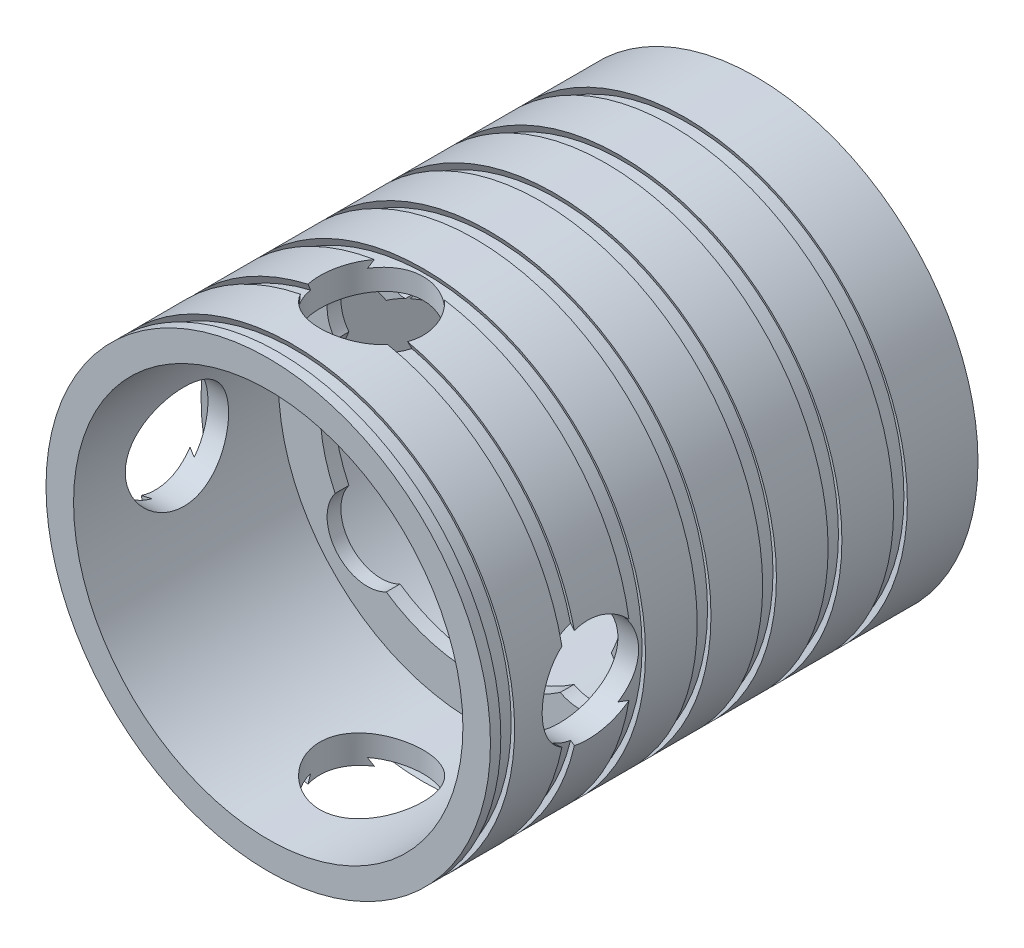
SolidWorks part; units mm, degrees
material "PA Type 6"
ref_plane "Front Plane" through (0, 0, 0) normal (0, 0, 1) x (1, 0, 0)
ref_plane "Top Plane" through (0, 0, 0) normal (0, 1, 0) x (1, 0, 0)
ref_plane "Right Plane" through (0, 0, 0) normal (1, 0, 0) x (0, 0, -1)
sketch "main_features" plane through (0, 0, 0) normal (0, 0, 1) x (1, 0, 0)
  line L0 (0, -22.25) -> (0, 22.25) construction
  line L1 (-22.25, 0) -> (22.25, 0) construction
  line L2 (10.9973, -19.3422) -> (-10.9973, -19.3422)
  line L3 (10.9973, 19.3422) -> (-10.9973, 19.3422)
  line L4 (-27.25, -7.4498) -> (-27.25, 7.4498)
  line L5 (27.25, -7.4498) -> (27.25, 7.4498)
  line L7 (-27, -7.2801) -> (-27, 7.2801) construction
  circle A0 centre (0, 0) radius 28.25
  circle A1 centre (0, 0) radius 32.25
  circle A2 centre (0, 0) radius 22.25
  circle A3 centre (-10.1595, 21.5294) radius 1.6
  arc A4 (26.963, 7.5497) -> (-26.963, 7.5497) centre (0, 0) ccw construction
  circle A11 centre (-10.1595, 21.5294) radius 1.6 construction
  circle A12 centre (-15.3592, 13.1518) radius 5.8499
  circle A13 centre (-15.3592, 13.1518) radius 5.8499 construction
  circle A14 centre (15.3592, 13.1518) radius 5.6
  circle A15 centre (15.3592, 13.1518) radius 5.6 construction
  circle A16 centre (-15.3592, -13.1518) radius 5.8499
  circle A17 centre (15.3592, -13.1518) radius 5.8499
  circle A18 centre (15.3592, 13.1518) radius 5.8499
  dimension "D1" = 6
  dimension "D2" = 4
  dimension "D3" = 0.25
  dimension "D4" = 0.25
extrude "front_sleeve" add sketch "main_features" against normal up to surface (39 mm away) contours A1 A0 | L5 A0 | L4 A0 region at (-27.6506, 0, 0) region at (27.6506, 0, 0) region at (-31.3378, 0, 0)
extrude "middle_flange" add sketch "Sketch1<3>" along normal blind 2 contours A1 A0 | L4 A0 | L5 A0 L4 A2 A18 A17 A16 A12 A3 | L5 A0 region at (-27.6506, 0, 0) region at (-26.465, 0, 0) region at (27.6506, 0, 0) region at (-31.3378, 0, 0)
sketch "Sketch1<3>" plane through (0, 0, 0) normal (0, 0, 1) x (1, 0, 0) same geometry as "main_features"
extrude "back_sleeve" add sketch "Sketch1<4>" along normal blind 31.75 contours A1 A0 region at (-31.3378, 0, 0)
sketch "Sketch1<4>" plane through (0, 0, 0) normal (0, 0, 1) x (1, 0, 0) same geometry as "main_features"
sketch "Sketch2" plane through (0, 0, 0) normal (1, 0, 0) x (0, 0, -1)
  line L0 (-29.25, 32.25) -> (-29.25, 31.25) construction
  line L1 (-18.25, 31.25) -> (-21.25, 31.25)
  line L2 (-18.25, 31.25) -> (-18.75, 32.25)
  line L3 (-18.75, 32.25) -> (-20.75, 32.25)
  line L4 (-21.25, 31.25) -> (-20.75, 32.25)
  line L6 (-27.75, 31.25) -> (-30.75, 31.25)
  line L7 (-27.75, 31.25) -> (-28.25, 32.25)
  line L8 (-28.25, 32.25) -> (-30.25, 32.25)
  line L9 (-30.75, 31.25) -> (-30.25, 32.25)
  line L10 (-31.75, 32.25) -> (39, 32.25) construction
  line L11 (39, 32.25) -> (-31.75, 32.25) construction
  line L12 (-18.25, 31.25) -> (-20.75, 32.25) construction
  line L13 (-18.75, 32.25) -> (-21.25, 31.25) construction
  line L14 (-8.75, 31.25) -> (-11.75, 31.25)
  line L15 (-8.75, 31.25) -> (-9.25, 32.25)
  line L16 (-9.25, 32.25) -> (-11.25, 32.25)
  line L17 (-11.75, 31.25) -> (-11.25, 32.25)
  line L18 (-8.75, 31.25) -> (-11.25, 32.25) construction
  line L19 (-9.25, 32.25) -> (-11.75, 31.25) construction
  line L20 (0.75, 31.25) -> (-2.25, 31.25)
  line L21 (0.75, 31.25) -> (0.25, 32.25)
  line L22 (0.25, 32.25) -> (-1.75, 32.25)
  line L23 (-2.25, 31.25) -> (-1.75, 32.25)
  line L24 (0.75, 31.25) -> (-1.75, 32.25) construction
  line L25 (0.25, 32.25) -> (-2.25, 31.25) construction
  line L26 (10.25, 31.25) -> (7.25, 31.25)
  line L27 (10.25, 31.25) -> (9.75, 32.25)
  line L28 (9.75, 32.25) -> (7.75, 32.25)
  line L29 (7.25, 31.25) -> (7.75, 32.25)
  line L30 (10.25, 31.25) -> (7.75, 32.25) construction
  line L31 (9.75, 32.25) -> (7.25, 31.25) construction
  line L32 (19.75, 31.25) -> (16.75, 31.25)
  line L33 (19.75, 31.25) -> (19.25, 32.25)
  line L34 (19.25, 32.25) -> (17.25, 32.25)
  line L35 (16.75, 31.25) -> (17.25, 32.25)
  line L36 (19.75, 31.25) -> (17.25, 32.25) construction
  line L37 (19.25, 32.25) -> (16.75, 31.25) construction
  line L38 (29.25, 31.25) -> (26.25, 31.25)
  line L39 (29.25, 31.25) -> (28.75, 32.25)
  line L40 (28.75, 32.25) -> (26.75, 32.25)
  line L41 (26.25, 31.25) -> (26.75, 32.25)
  line L42 (29.25, 31.25) -> (26.75, 32.25) construction
  line L43 (28.75, 32.25) -> (26.25, 31.25) construction
  line L44 (-31.75, 32.25) -> (-31.75, -32.25) construction
  point P0 (-19.8627, 45.7344)
  point P8 (-9.8627, 45.7344)
  point P18 (0.1373, 45.7344)
  point P23 (10.1373, 45.7344)
  point P28 (20.1373, 45.7344)
  point P33 (30.1373, 45.7344)
  dimension "D1" = 3
  dimension "D3" = 2
  dimension "D4" = 1
  dimension "D5" = 1
  dimension "D2" = 7
ref_axis "center_axis" through (0, 0, -39) along (0, 0, 1)
revolve "silicone_grooves" cut sketch "Sketch2" angle 360 about axis through (0, 0, -39) along (0, 0, 1)
sketch "Sketch7" plane through (0, 0, 0) normal (1, 0, 0) x (0, 0, -1)
  line L0 (-31.75, 0) -> (39, 0) construction
  line L1 (39, -32.25) -> (39, 32.25) construction
  line L2 (-31.75, 32.25) -> (-31.75, -32.25) construction
  circle A0 centre (-16.75, 0) radius 7.5
  dimension "D1" = 15
  dimension "D2" = 15
extrude "silicone_holes1" cut sketch "Sketch7" against normal through all both and the other way through all
sketch "Sketch8" plane through (0, 0, 0) normal (0, 1, 0) x (1, 0, 0)
  line L0 (0, -31.75) -> (0, 39) construction
  line L3 (-32.25, -31.75) -> (32.25, -31.75) construction
  line L4 (28.25, 39) -> (-28.25, 39) construction
  circle A0 centre (0, -16.75) radius 7.5
  dimension "D1" = 15
  dimension "D2" = 15
extrude "silicone_holes2" cut sketch "Sketch8" against normal through all both and the other way through all
